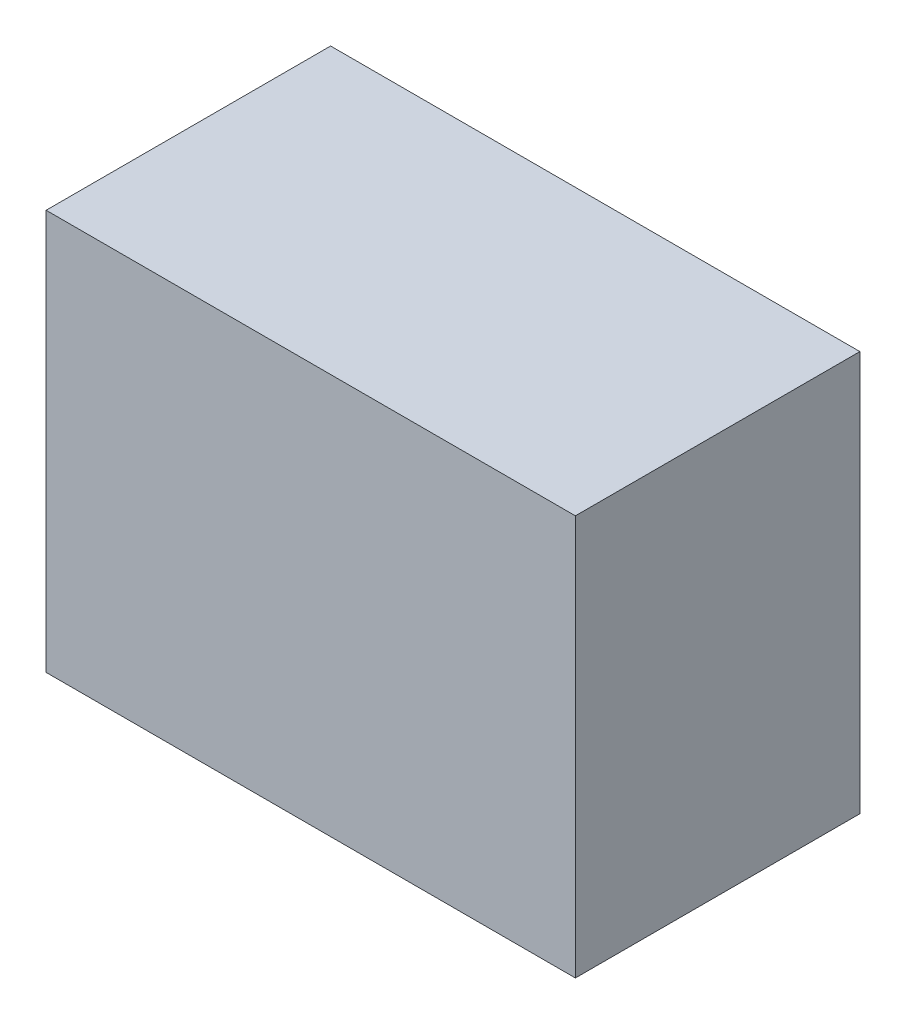
SolidWorks part; units mm, degrees
ref_plane "Front Plane" through (0, 0, 0) normal (0, 0, 1) x (1, 0, 0)
ref_plane "Top Plane" through (0, 0, 0) normal (0, 1, 0) x (1, 0, 0)
ref_plane "Right Plane" through (0, 0, 0) normal (1, 0, 0) x (0, 0, -1)
sketch "Sketch1" plane through (0, 0, 0) normal (0, 1, 0) x (1, 0, 0)
  line L1 (-160, -86) -> (160, -86)
  line L2 (-160, -86) -> (-160, 86)
  line L3 (-160, 86) -> (160, 86)
  line L4 (160, -86) -> (160, 86)
  line L5 (-160, -86) -> (160, 86) construction
  line L6 (-160, 86) -> (160, -86) construction
  point P0 (0, 0)
  dimension "D1" = 172
  dimension "D2" = 320
extrude "Boss-Extrude1" add sketch "Sketch1" along normal blind 242
